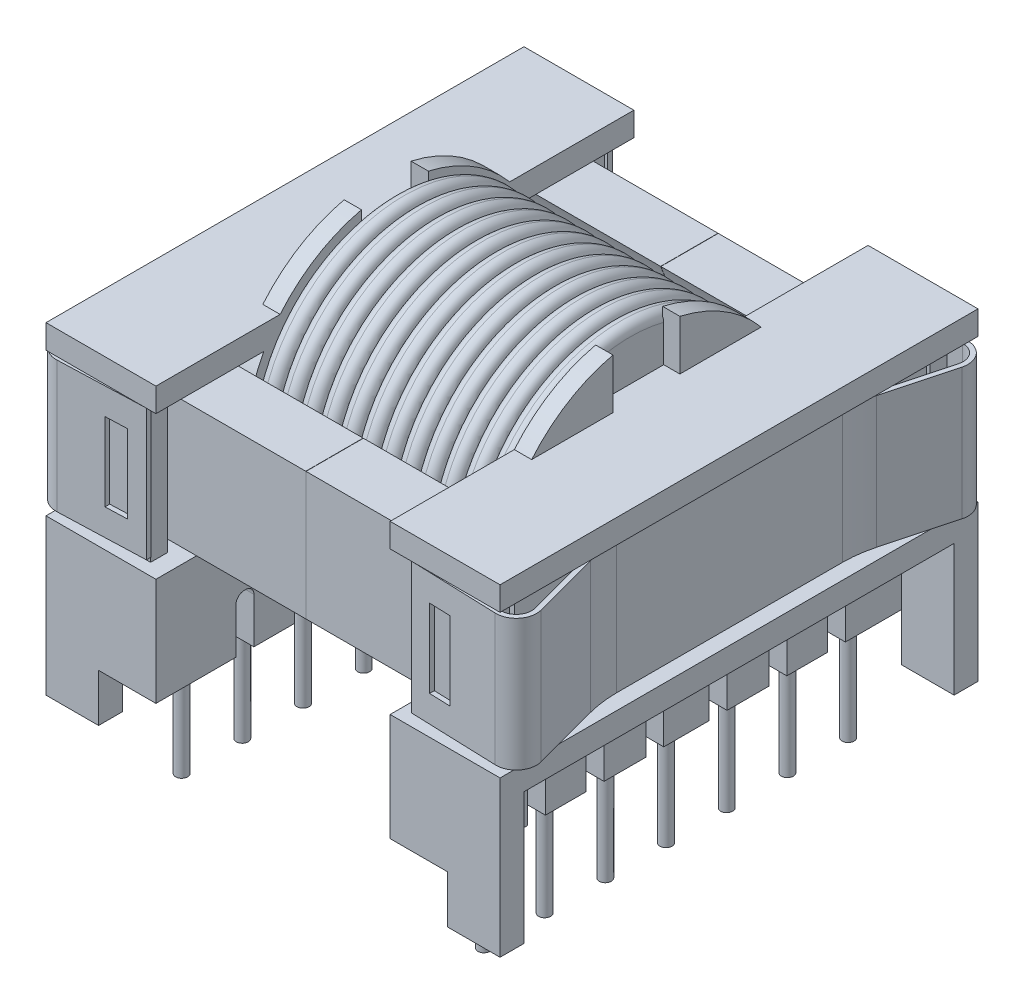
SolidWorks part; units mm, degrees
ref_plane "Front Plane" through (0, 0, 0) normal (0, 0, 1) x (1, 0, 0)
ref_plane "Top Plane" through (0, 0, 0) normal (0, 1, 0) x (1, 0, 0)
ref_plane "Right Plane" through (0, 0, 0) normal (1, 0, 0) x (0, 0, -1)
sketch "Sketch2" plane through (0, 0, 0) normal (1, 0, 0) x (0, 0, -1)
  circle A0 centre (0, 27.3777) radius 6.75
  circle A1 centre (0, 27.3777) radius 5.7
  dimension "D1" = 13.5
  dimension "D2" = 11.4
extrude "Boss-Extrude1" add sketch "Sketch2" along normal mid plane 22.5
sketch "Sketch3" plane through (11.25, 0, 0) normal (1, 0, 0) x (0, 0, -1)
  line L0 (-2.8, 42.3777) -> (-2.8, 39.5601) construction
  line L1 (-2.8, 42.3777) -> (2.8, 42.3777) construction
  line L2 (-2.8, 15.1953) -> (-2.8, 12.3777) construction
  line L3 (-2.8, 12.3777) -> (2.8, 12.3777) construction
  line L4 (2.8, 15.1953) -> (2.8, 12.3777) construction
  line L5 (0, 27.3777) -> (1.2386, 20.7423) construction
  line L6 (-1.2386, 20.7423) -> (0, 27.3777) construction
  line L7 (-2.8, 42.3777) -> (-2.2937, 39.6654) construction
  line L8 (2.2937, 39.6654) -> (2.8, 42.3777) construction
  line L9 (2.8, 42.3777) -> (2.8, 39.5601) construction
  line L10 (-2.2937, 39.6654) -> (0, 27.3777) construction
  line L11 (-2.8, 39.5601) -> (-2.8, 21.2358) construction
  line L12 (0, 27.3777) -> (2.2937, 39.6654) construction
  line L13 (2.8, 39.5601) -> (2.8, 21.2358) construction
  line L14 (-2.8, 12.3777) -> (-2.2937, 15.0899) construction
  line L15 (2.2937, 15.0899) -> (2.8, 12.3777) construction
  line L16 (-2.8, 39.5601) -> (-2.8, 32.3426)
  line L17 (0, 52.6668) -> (0, 20.6277) construction
  line L18 (-16.7617, 27.3777) -> (15.0434, 27.3777) construction
  line L19 (2.8, 39.5601) -> (2.8, 32.3426)
  line L20 (2.8, 21.2358) -> (2.8, 22.4128)
  line L21 (-2.8, 21.2358) -> (-2.8, 22.4128)
  line L22 (2.8, 21.2358) -> (2.8, 15.1953) construction
  line L23 (2.8, 15.1953) -> (2.8, 21.2358) construction
  line L24 (1.2386, 20.7423) -> (2.2937, 15.0899) construction
  line L25 (0, 20.6277) -> (0, 14.8777) construction
  line L26 (0, 14.8777) -> (0, 0) construction
  line L27 (-2.2937, 15.0899) -> (-1.2386, 20.7423) construction
  line L28 (-2.8, 21.2358) -> (-2.8, 15.1953) construction
  line L29 (-2.8, 15.1953) -> (-2.8, 21.2358) construction
  arc A0 (-2.8, 39.5601) -> (-2.8, 15.1953) centre (0, 27.3777) ccw
  arc A1 (2.2937, 39.6654) -> (-2.2937, 39.6654) centre (0, 27.3777) ccw construction
  arc A2 (-2.2937, 15.0899) -> (2.2937, 15.0899) centre (0, 27.3777) ccw construction
  arc A3 (2.8, 15.1953) -> (2.8, 39.5601) centre (0, 27.3777) ccw
  arc A4 (2.2937, 15.0899) -> (2.8, 15.1953) centre (0, 27.3777) ccw construction
  arc A5 (-2.8, 15.1953) -> (-2.2937, 15.0899) centre (0, 27.3777) ccw construction
  arc A6 (-2.2937, 39.6654) -> (-2.8, 39.5601) centre (0, 27.3777) ccw construction
  arc A7 (2.8, 39.5601) -> (2.2937, 39.6654) centre (0, 27.3777) ccw construction
  circle A8 centre (0, 27.3777) radius 5.7 construction
  arc A9 (-2.8, 22.4128) -> (-2.8, 32.3426) centre (0, 27.3777) cw
  arc A10 (2.8, 32.3426) -> (2.8, 22.4128) centre (0, 27.3777) cw
  arc A11 (-2.8, 21.2358) -> (2.8, 21.2358) centre (0, 27.3777) ccw
  circle A12 centre (0, 27.3777) radius 6.75 construction
  arc A13 (-2.8, 15.1953) -> (2.8, 15.1953) centre (0, 27.3777) ccw
  dimension "D1" = 25
  dimension "D2" = 5.6
  dimension "D3" = 30
extrude "Boss-Extrude2" add sketch "Sketch3" against normal blind 1.45 separate body
sketch "Sketch4" plane through (9.8, 0, 0) normal (1, 0, 0) x (0, 0, -1)
  line L0 (0, 0) -> (0, 49.5865) construction
  line L1 (-20, 35.3777) -> (20, 35.3777)
  line L2 (20, 33.3777) -> (-20, 33.3777)
  line L3 (-20, 35.3777) -> (-20, 33.3777)
  line L4 (20, 35.3777) -> (20, 33.3777)
  line L5 (5.7, 27.3777) -> (-5.7, 27.3777) construction
  line L6 (-18, 19.3777) -> (18, 19.3777)
  line L7 (-20, 19.3777) -> (-20, 21.3777)
  line L8 (20, 21.3777) -> (-20, 21.3777)
  line L9 (20, 19.3777) -> (20, 21.3777)
  line L10 (20, 21.3777) -> (20, 8.3777)
  line L11 (20, 8.3777) -> (18, 8.3777)
  line L12 (18, 8.3777) -> (18, 19.3777)
  line L13 (18, 19.3777) -> (20, 19.3777) construction
  line L14 (18, 19.3777) -> (18, 21.3777) construction
  line L15 (-20, 21.3777) -> (-20, 8.3777) construction
  line L16 (-20, 8.3777) -> (-18, 8.3777)
  line L17 (-18, 8.3777) -> (-18, 19.3777)
  line L18 (-20, 19.3777) -> (-18, 19.3777) construction
  line L19 (-20, 19.3777) -> (-20, 8.3777)
  circle A1 centre (0, 27.3777) radius 5.7 construction
  arc A2 (2.8, 22.4128) -> (2.8, 32.3426) centre (0, 27.3777) ccw construction
  point P6 (0, 35.3777)
  line M27 (-2.8, 39.5601) -> (-2.8, 32.3426)
  line M29 (2.8, 32.3426) -> (2.8, 39.5601)
  arc M30 (2.8, 39.5601) -> (-2.8, 39.5601) centre (0, 27.3777) cw
  dimension "D4" = 12
  dimension "D2" = 40
  dimension "D3" = 2
  dimension "D5" = 13
  dimension "D6" = 2
extrude "Boss-Extrude3" add sketch "Sketch4" along normal blind 9.2 separate body contours L3 L1 L2 M30 | L2 L1 M27 M29 | L2 L1 M30 M27 | L2 L1 M30 M29 | L1 L4 L2 M30 | L11 L12 L6 L8 L9 L10 M30 | L8 L6 M30 | L19 L7 L8 L6 L17 L16 M30 | L8 L7 L19 L16 L17 L6 L12 L11 L10 region at (9.8, 34.4011, 15.1583) region at (9.8, 34.3477, 6.5765) region at (9.8, 34.3777, 0) region at (9.8, 34.3477, -6.5765) region at (9.8, 20.251, 10.4714) region at (9.8, 20.3996, 0) region at (9.8, 34.4011, -15.1583) region at (9.8, 21.2112, -15.4829)
sketch "Sketch5" plane through (11.25, 0, 0) normal (1, 0, 0) x (0, 0, -1)
  line L0 (0, 0) -> (0, 54.3) construction
  line L1 (-17.6, 33.3777) -> (-17.6, 21.3777)
  line L4 (-17.6, 21.3777) -> (-19, 21.3777)
  line L5 (-19, 21.3777) -> (-19, 33.3777)
  line L6 (-19, 33.3777) -> (-17.6, 33.3777)
  line L7 (19, 21.3777) -> (19, 33.3777)
  line L8 (17.6, 21.3777) -> (19, 21.3777)
  line L9 (17.6, 33.3777) -> (17.6, 21.3777)
  line L10 (19, 33.3777) -> (17.6, 33.3777)
  line L14 (20, 33.3777) -> (-20, 33.3777) construction
  line L15 (20, 21.3777) -> (-20, 21.3777) construction
  dimension "D1" = 38
  dimension "D2" = 1.4
extrude "Boss-Extrude4" add sketch "Sketch5" along normal blind 6.15
sketch "Sketch6" plane through (0, 0, -20) normal (0, 0, -1) x (-1, 0, 0)
  line L1 (-9.8, 8.3777) -> (-14.6, 8.3777)
  line L2 (-9.8, 8.3777) -> (-9.8, 12.3777)
  line L3 (-9.8, 12.3777) -> (-14.6, 12.3777)
  line L4 (-14.6, 8.3777) -> (-14.6, 12.3777)
  line M8 (-19, 8.3777) -> (-9.8, 8.3777)
  dimension "D1" = 4
  dimension "D2" = 4.8
extrude "Cut-Extrude1" cut sketch "Sketch6" against normal through all both and the other way through all contours L4 L2 L3 M8 region at (12.2, 10.3777, -20)
sketch "Sketch9" plane through (0, 0, 0) normal (0, 0, 1) x (1, 0, 0)
  line L0 (14.6, 12.3777) -> (9.8, 12.3777) construction
  line L1 (9.8, 12.3777) -> (14.6, 12.3777)
  line L2 (9.8, 12.3777) -> (9.8, 19.3777)
  line L3 (9.8, 19.3777) -> (14.6, 19.3777)
  line L4 (14.6, 12.3777) -> (14.6, 19.3777)
  line L5 (9.8, 12.3777) -> (9.8, 19.3777) construction
  line L6 (19, 19.3777) -> (9.8, 19.3777) construction
  line L7 (14.6, 12.3777) -> (14.6, 8.3777) construction
extrude "Boss-Extrude5" add sketch "Sketch9" along normal up to surface and the other way up to surface separate body up to face at (14.4667, 13.3777, 18) other way up to face at (14.4667, 13.3777, -18)
sketch "Sketch10" plane through (14.6, 0, 0) normal (1, 0, 0) x (0, 0, -1)
  line L0 (-18, 12.3777) -> (18, 12.3777) construction
  line L1 (-13.3, 12.3777) -> (-11.8, 12.3777)
  line L2 (-13.3, 12.3777) -> (-13.3, 16.1877)
  line L3 (-12.61, 16.8777) -> (-12.49, 16.8777)
  line L4 (-11.8, 12.3777) -> (-11.8, 16.1877)
  line L5 (-18, 8.3777) -> (-18, 19.3777) construction
  line L6 (-6.9, 12.3777) -> (-8.4, 12.3777)
  line L7 (-6.9, 12.3777) -> (-6.9, 17.1877)
  line L8 (-7.59, 17.8777) -> (-7.71, 17.8777)
  line L9 (-8.4, 12.3777) -> (-8.4, 17.1877)
  line L10 (0, 0) -> (0, 35.3777) construction
  line L11 (-3.4, 12.3777) -> (-1.9, 12.3777)
  line L12 (-3.4, 12.3777) -> (-3.4, 18.2877)
  line L13 (-2.71, 18.9777) -> (-2.59, 18.9777)
  line L14 (-1.9, 12.3777) -> (-1.9, 18.2877)
  line L15 (-20, 35.3777) -> (20, 35.3777) construction
  line L16 (1.9, 12.3777) -> (1.9, 18.2877)
  line L17 (2.71, 18.9777) -> (2.59, 18.9777)
  line L18 (3.4, 12.3777) -> (3.4, 18.2877)
  line L19 (3.4, 12.3777) -> (1.9, 12.3777)
  line L20 (8.4, 12.3777) -> (8.4, 17.1877)
  line L21 (7.59, 17.8777) -> (7.71, 17.8777)
  line L22 (6.9, 12.3777) -> (6.9, 17.1877)
  line L23 (6.9, 12.3777) -> (8.4, 12.3777)
  line L24 (11.8, 12.3777) -> (11.8, 16.1877)
  line L25 (12.61, 16.8777) -> (12.49, 16.8777)
  line L26 (13.3, 12.3777) -> (13.3, 16.1877)
  line L27 (13.3, 12.3777) -> (11.8, 12.3777)
  arc A0 (13.3, 16.1877) -> (12.61, 16.8777) centre (12.61, 16.1877) ccw
  arc A1 (11.8, 16.1877) -> (12.49, 16.8777) centre (12.49, 16.1877) cw
  arc A2 (7.71, 17.8777) -> (8.4, 17.1877) centre (7.71, 17.1877) cw
  arc A3 (6.9, 17.1877) -> (7.59, 17.8777) centre (7.59, 17.1877) cw
  arc A4 (2.71, 18.9777) -> (3.4, 18.2877) centre (2.71, 18.2877) cw
  arc A5 (1.9, 18.2877) -> (2.59, 18.9777) centre (2.59, 18.2877) cw
  arc A6 (-1.9, 18.2877) -> (-2.59, 18.9777) centre (-2.59, 18.2877) ccw
  arc A7 (-3.4, 18.2877) -> (-2.71, 18.9777) centre (-2.71, 18.2877) cw
  arc A8 (-7.59, 17.8777) -> (-6.9, 17.1877) centre (-7.59, 17.1877) cw
  arc A9 (-8.4, 17.1877) -> (-7.71, 17.8777) centre (-7.71, 17.1877) cw
  arc A10 (-11.8, 16.1877) -> (-12.49, 16.8777) centre (-12.49, 16.1877) ccw
  arc A11 (-13.3, 16.1877) -> (-12.61, 16.8777) centre (-12.61, 16.1877) cw
  point P35 (13.3, 16.8777)
  point P38 (11.8, 16.8777)
  point P41 (8.4, 17.8777)
  point P44 (6.9, 17.8777)
  point P47 (3.4, 18.9777)
  point P50 (1.9, 18.9777)
  point P53 (-1.9, 18.9777)
  point P56 (-3.4, 18.9777)
  point P59 (-6.9, 17.8777)
  point P62 (-8.4, 17.8777)
  point P65 (-11.8, 16.8777)
  point P68 (-13.3, 16.8777)
  dimension "D10" = 0.69
  dimension "D1" = 4.7
  dimension "D2" = 1.5
  dimension "D3" = 4.5
  dimension "D4" = 3.4
  dimension "D5" = 5.5
  dimension "D6" = 1.5
  dimension "D7" = 3.5
  dimension "D8" = 6.6
  dimension "D9" = 1.5
extrude "Cut-Extrude2" cut sketch "Sketch10" against normal through all both and the other way through all
mirror "Mirror1" about plane through (0, 0, 0) normal (1, 0, 0) of bodies 112 106 105 104 110 102
combine bodies "Combine1" operation type add bodies to combine 101 102 110 104 105 112 113 114 106 115 116 117 118
sketch "Sketch11" plane through (0, 12.3777, 0) normal (0, -1, 0) x (1, 0, 0)
  line L0 (0, 0) -> (0, 18.641) construction
  line L1 (-25.8212, 0) -> (25.8212, 0) construction
  line L2 (13.15, 15) -> (13.15, 22.8893) construction
  line L3 (12.65, 15.5) -> (7.1354, 15.5) construction
  line L4 (9.8, 20) -> (14.6, 20) construction
  line L5 (-12.65, 15.5) -> (-7.1354, 15.5) construction
  line L6 (-13.15, 15) -> (-13.15, 22.8893) construction
  circle A0 centre (12.65, 15) radius 0.5
  circle A1 centre (12.65, 9.92) radius 0.5
  circle A2 centre (12.65, 4.84) radius 0.5
  circle A3 centre (12.65, -0.24) radius 0.5
  circle A4 centre (12.65, -5.32) radius 0.5
  circle A5 centre (12.65, -10.4) radius 0.5
  circle A6 centre (12.65, -15.48) radius 0.5
  circle A7 centre (-12.65, -15.48) radius 0.5
  circle A8 centre (-12.65, -10.4) radius 0.5
  circle A9 centre (-12.65, -5.32) radius 0.5
  circle A10 centre (-12.65, -0.24) radius 0.5
  circle A11 centre (-12.65, 4.84) radius 0.5
  circle A12 centre (-12.65, 9.92) radius 0.5
  circle A13 centre (-12.65, 15) radius 0.5
  dimension "D1" = 13.15
  dimension "D2" = 1
  dimension "D4" = 4.5
  dimension "D3" = 7
extrude "Boss-Extrude6" add sketch "Sketch11" along normal blind 9
sketch "Sketch12" plane through (0, 0, 0) normal (1, 0, 0) x (0, 0, -1)
  line L0 (17.25, 32.7277) -> (17.25, 22.0277)
  line L1 (0, 27.3777) -> (22.7283, 27.3777) construction
  line L2 (0, 27.3777) -> (0, 47.8275) construction
  line L3 (17.25, 32.7277) -> (12.4491, 32.7277)
  line L4 (17.25, 22.0277) -> (12.4491, 22.0277)
  line L5 (-17.25, 32.7277) -> (-17.25, 22.0277)
  line L6 (-17.25, 22.0277) -> (-12.4491, 22.0277)
  line L7 (-17.25, 32.7277) -> (-12.4491, 32.7277)
  circle A0 centre (0, 27.3777) radius 5.4
  circle A1 centre (0, 27.3777) radius 5.7 construction
  arc A2 (-12.4491, 32.7277) -> (-12.4491, 22.0277) centre (0, 27.3777) ccw
  arc A3 (0, 40.9277) -> (-12.4491, 32.7277) centre (0, 27.3777) ccw construction
  arc A4 (-12.4491, 22.0277) -> (12.4491, 22.0277) centre (0, 27.3777) ccw construction
  arc A5 (12.4491, 22.0277) -> (12.4491, 32.7277) centre (0, 27.3777) ccw
  arc A6 (12.4491, 32.7277) -> (0, 40.9277) centre (0, 27.3777) ccw construction
  point P7 (17.25, 27.3777)
  dimension "D1" = 10.8
  dimension "D2" = 27.1
  dimension "D3" = 34.5
  dimension "D4" = 10.7
extrude "Boss-Extrude7" add sketch "Sketch12" along normal blind 12.15 from offset 0.01 separate body
sketch "Sketch13" plane through (12.16, 0, 0) normal (1, 0, 0) x (0, 0, -1)
  line L0 (12.4491, 22.0277) -> (17.25, 22.0277) construction
  line L1 (-17.25, 32.7277) -> (17.25, 32.7277)
  line L2 (-17.25, 32.7277) -> (-17.25, 22.0277)
  line L3 (-17.25, 22.0277) -> (17.25, 22.0277)
  line L4 (17.25, 32.7277) -> (17.25, 22.0277)
  line L5 (17.25, 22.0277) -> (17.25, 32.7277) construction
extrude "Boss-Extrude8" add sketch "Sketch13" along normal blind 5.3
sketch "Sketch14" plane through (0, 21.3777, 0) normal (0, 1, 0) x (1, 0, 0)
  line L0 (0, 0) -> (33.7839, 0) construction
  line L1 (18.0058, 9.4417) -> (18.0058, -9.4417)
  line L2 (18.3465, 12.0299) -> (19.8558, 17.6627)
  line L3 (18.3542, 19.55) -> (11.1033, 19.2948)
  line L4 (11.25, 19.3) -> (11.25, 19) construction
  line L5 (18.3465, -12.0299) -> (19.8558, -17.6627)
  line L6 (18.3542, -19.55) -> (11.1033, -19.2948)
  arc A0 (19.8558, 17.6627) -> (18.3542, 19.55) centre (18.4069, 18.0509) ccw
  arc A1 (18.0058, 9.4417) -> (18.3465, 12.0299) centre (28.0058, 9.4417) cw
  arc A2 (18.0058, -9.4417) -> (18.3465, -12.0299) centre (28.0058, -9.4417) ccw
  arc A3 (19.8558, -17.6627) -> (18.3542, -19.55) centre (18.4069, -18.0509) cw
  point P6 (18.0058, 0)
  point P9 (19.4352, 18.8376)
  point P10 (18.5076, 18.0596)
  point P17 (18.0058, 10.7583)
  point P18 (11.1033, 19.3)
  dimension "D3" = 165
  dimension "D5" = 1.5
  dimension "D7" = 10
  dimension "D1" = 18.0058
  dimension "D2" = 20.2
  dimension "D4" = 0.3
  dimension "D6" = 39.1
extrude "Extrude-Thin1" add sketch "Sketch14" along normal blind 11 from offset 0.5 separate body thin thin type mid plane wall 0.4
sketch "Sketch15" plane through (-0.6715, 0, -19.0806) normal (-0.0352, 0, -0.9994) x (-0.9994, 0, 0.0352)
  line L0 (-11.775, 32.8777) -> (-11.775, 21.8777) construction
  line L1 (-15.125, 30.6527) -> (-13.325, 30.6527)
  line L2 (-15.125, 30.6527) -> (-15.125, 24.1027)
  line L3 (-15.125, 24.1027) -> (-13.325, 24.1027)
  line L4 (-13.325, 30.6527) -> (-13.325, 24.1027)
  line L5 (-15.125, 30.6527) -> (-13.325, 24.1027) construction
  line L6 (-15.125, 24.1027) -> (-13.325, 30.6527) construction
  line L7 (-11.775, 27.3777) -> (-19.0304, 27.3777) construction
  line L8 (-19.0304, 32.8777) -> (-19.0304, 21.8777) construction
  point P0 (-14.225, 27.3777)
  point P11 (0, 0)
  dimension "D1" = 1.55
  dimension "D2" = 6.55
  dimension "D3" = 1.8
extrude "Cut-Extrude3" cut sketch "Sketch15" against normal mid plane 11
mirror "Mirror2" about plane through (0, 0, 0) normal (0, 0, 1) of "Cut-Extrude3"
mirror "Mirror3" about plane through (0, 0, 0) normal (1, 0, 0) of bodies 124 127
sketch "Sketch16" plane through (0, 0, 0) normal (1, 0, 0) x (0, 0, -1)
  circle A0 centre (0, 27.3777) radius 7
  circle A1 centre (0, 27.3777) radius 12.2
  dimension "D1" = 14
  dimension "D2" = 24.4
extrude "Boss-Extrude9" add sketch "Sketch16" along normal blind 1.55 from surface separate body starting at face at (-9.8, 20.4645, 0)
fillet "Fillet1" radius 0.775 2 edges at (-9.8, 27.3777, 12.2) (-8.25, 27.3777, 12.2)
pattern_linear "LPattern1" count 12 spacing 1.65 along (1, 0, 0) of bodies 130
